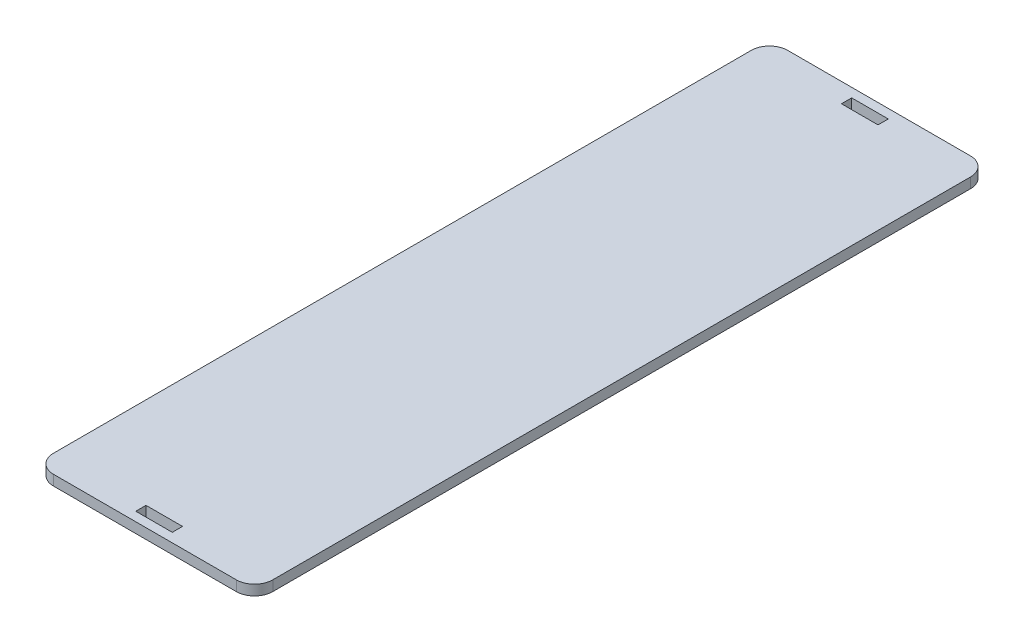
SolidWorks part; units mm, degrees
material "t5ハニカムプラダン"
ref_plane "正面" through (0, 0, 0) normal (0, 0, 1) x (1, 0, 0)
ref_plane "平面" through (0, 0, 0) normal (0, 1, 0) x (1, 0, 0)
ref_plane "右側面" through (0, 0, 0) normal (1, 0, 0) x (0, 0, -1)
sketch "ｽｹｯﾁ1" plane through (0, 0, 0) normal (0, 1, 0) x (1, 0, 0)
  line L0 (0, -200.9) -> (0, 0) construction
  line L1 (-60, 200.9) -> (60, 200.9)
  line L2 (-60, 200.9) -> (-60, -200.9)
  line L3 (-60, -200.9) -> (60, -200.9)
  line L4 (60, 200.9) -> (60, -200.9)
  line L5 (-60, 200.9) -> (60, -200.9) construction
  line L6 (-60, -200.9) -> (60, 200.9) construction
  line L7 (0, 0) -> (60, 0) construction
  line L8 (-10, 195.9) -> (10, 190.3) construction
  line L9 (-10, -190.3) -> (10, -190.3)
  line L10 (-10, -190.3) -> (-10, -195.9)
  line L11 (-10, -195.9) -> (10, -195.9)
  line L12 (10, -190.3) -> (10, -195.9)
  line L13 (-10, -190.3) -> (10, -195.9) construction
  line L14 (-10, -195.9) -> (10, -190.3) construction
  line L15 (-10, 190.3) -> (10, 195.9) construction
  line L16 (10, 190.3) -> (10, 195.9)
  line L17 (-10, 195.9) -> (10, 195.9)
  line L18 (-10, 190.3) -> (-10, 195.9)
  line L19 (-10, 190.3) -> (10, 190.3)
  point P0 (0, 0)
  point P9 (0, -193.1)
  point P18 (0, 193.1)
  dimension "D1" = 401.8
  dimension "D2" = 120
  dimension "D3" = 20
  dimension "D4" = 5.6
  dimension "D5" = 5
extrude "ﾎﾞｽ - 押し出し1" add sketch "ｽｹｯﾁ1" along normal blind 5.6
fillet "ﾌｨﾚｯﾄ1" radius 10 4 edges at (-60, 2.8, -200.9) (60, 2.8, -200.9) (60, 2.8, 200.9) (-60, 2.8, 200.9)
